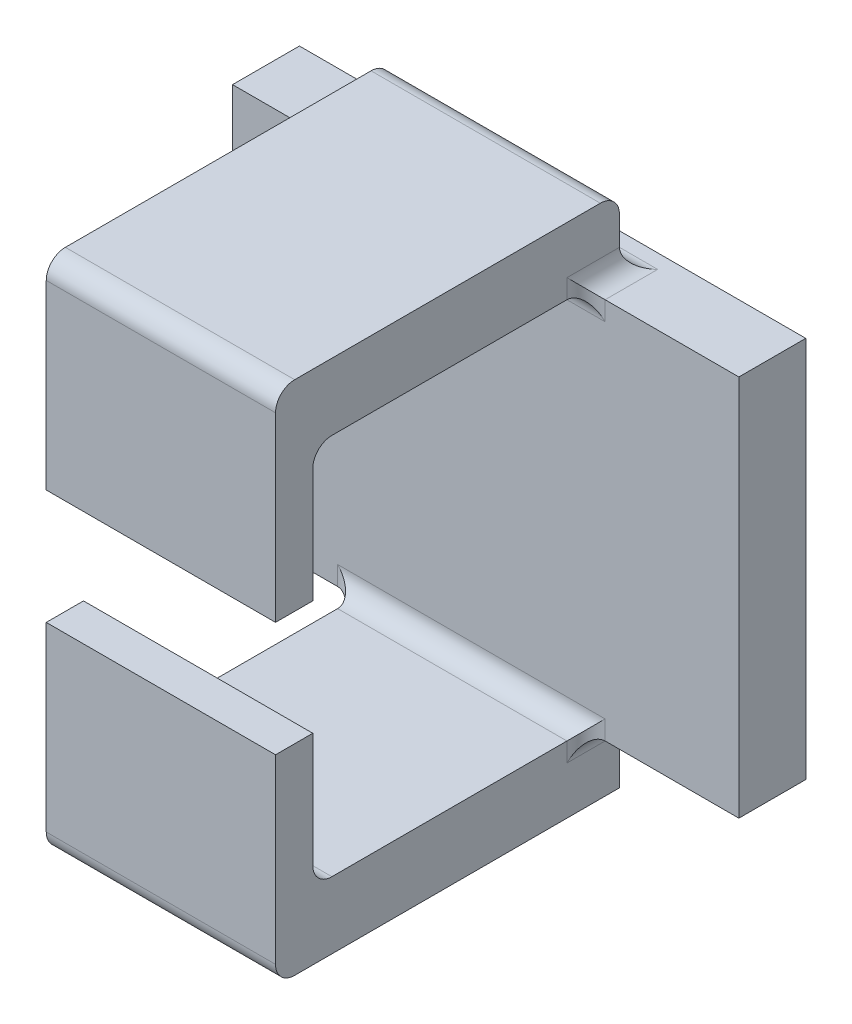
SolidWorks part; units mm, degrees
ref_plane "Front Plane" through (0, 0, 0) normal (0, 0, 1) x (1, 0, 0)
ref_plane "Top Plane" through (0, 0, 0) normal (0, 1, 0) x (1, 0, 0)
ref_plane "Right Plane" through (0, 0, 0) normal (1, 0, 0) x (0, 0, -1)
sketch "Sketch1" plane through (0, 0, 0) normal (0, 0, 1) x (1, 0, 0)
  line L1 (-13.25, 10) -> (13.25, 10)
  line L2 (-13.25, 10) -> (-13.25, -10)
  line L3 (-13.25, -10) -> (13.25, -10)
  line L4 (13.25, 10) -> (13.25, -10)
  line L5 (-13.25, 10) -> (13.25, -10) construction
  line L6 (-13.25, -10) -> (13.25, 10) construction
  point P0 (0, 0)
  dimension "D1" = 26.5
  dimension "D2" = 20
extrude "Boss-Extrude1" add sketch "Sketch1" along normal blind 3.5
sketch "Sketch2" plane through (0, 10, 0) normal (0, 1, 0) x (1, 0, 0)
  line L0 (13.25, -3.5) -> (13.25, 0) construction
  line L1 (5.25, -1.75) -> (-6.75, -1.75)
  line L2 (5.25, -1.75) -> (5.25, -19.75)
  line L3 (5.25, -19.75) -> (-6.75, -19.75)
  line L4 (-6.75, -1.75) -> (-6.75, -19.75)
  line L5 (13.25, 0) -> (-13.25, 0) construction
  dimension "D1" = 12
  dimension "D2" = 18
  dimension "D3" = 8
  dimension "D4" = 1.75
extrude "Boss-Extrude2" add sketch "Sketch2" along normal blind 3.5
fillet "Fillet1" radius 1 1 edges at (-0.75, 10, 1.75)
fillet "Fillet2" radius 1 1 edges at (-0.75, 10, 3.5)
sketch "Sketch3" plane through (0, -10, 0) normal (0, -1, 0) x (-1, 0, 0)
  line L0 (13.25, 0) -> (-13.25, 0) construction
  line L1 (-5.25, -1.75) -> (6.75, -1.75)
  line L2 (-5.25, -1.75) -> (-5.25, -19.75)
  line L3 (-5.25, -19.75) -> (6.75, -19.75)
  line L4 (6.75, -1.75) -> (6.75, -19.75)
  line L5 (-13.25, -3.5) -> (-13.25, 0) construction
  dimension "D1" = 12
  dimension "D2" = 1.75
  dimension "D3" = 8
  dimension "D4" = 18
extrude "Boss-Extrude3" add sketch "Sketch3" along normal blind 3.5
fillet "Fillet3" radius 1 1 edges at (-0.75, -10, 1.75)
fillet "Fillet4" radius 1 1 edges at (-0.75, -10, 3.5)
fillet "Fillet5" radius 1 1 edges at (5.25, 10, 2.125)
fillet "Fillet6" radius 1 1 edges at (-6.75, 10, 2.125)
fillet "Fillet7" radius 1 1 edges at (5.25, 10, 3.5)
fillet "Fillet8" radius 1 1 edges at (-6.75, 10, 3.5)
fillet "Fillet9" radius 1 1 edges at (-6.75, -10, 2.125)
fillet "Fillet10" radius 1 1 edges at (-6.75, -10, 3.5)
fillet "Fillet11" radius 1 1 edges at (5.25, -10, 2.125)
fillet "Fillet12" radius 1 1 edges at (5.25, -10, 3.5)
sketch "Sketch4" plane through (0, -10, 0) normal (0, 1, 0) x (1, 0, 0)
  line L0 (5.25, -4.5) -> (5.25, -19.75) construction
  line L1 (-6.75, -19.75) -> (5.25, -19.75)
  line L2 (-6.75, -19.75) -> (-6.75, -17.8)
  line L3 (-6.75, -17.8) -> (5.25, -17.8)
  line L4 (5.25, -19.75) -> (5.25, -17.8)
  dimension "D1" = 1.95
  dimension "D2" = 12
extrude "Boss-Extrude4" add sketch "Sketch4" along normal blind 7
sketch "Sketch5" plane through (0, 10, 0) normal (0, -1, 0) x (-1, 0, 0)
  line L0 (-5.25, -19.75) -> (-5.25, -4.5) construction
  line L1 (6.75, -19.75) -> (-5.25, -19.75)
  line L2 (6.75, -19.75) -> (6.75, -17.8)
  line L3 (6.75, -17.8) -> (-5.25, -17.8)
  line L4 (-5.25, -19.75) -> (-5.25, -17.8)
  dimension "D1" = 12
  dimension "D2" = 1.95
extrude "Boss-Extrude5" add sketch "Sketch5" along normal blind 7
fillet "Fillet13" radius 1 1 edges at (-0.75, 10, 17.8)
fillet "Fillet14" radius 1 1 edges at (-0.75, 13.5, 19.75)
fillet "Fillet15" radius 1 1 edges at (-0.75, 13.5, 1.75)
fillet "Fillet16" radius 1 1 edges at (-0.75, -13.5, 19.75)
fillet "Fillet17" radius 1 1 edges at (-0.75, -10, 17.8)
